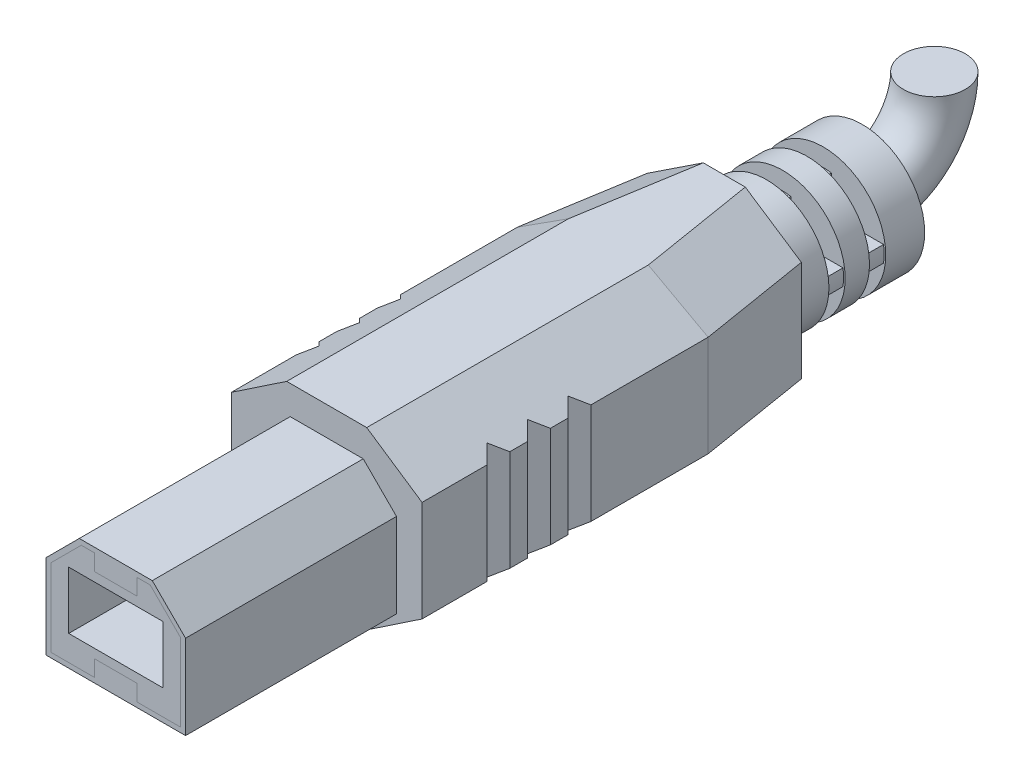
SolidWorks part; units mm, degrees
ref_plane "Front" through (0, 0, 0) normal (0, 0, 1) x (1, 0, 0)
ref_plane "Top" through (0, 0, 0) normal (0, 1, 0) x (1, 0, 0)
ref_plane "Right" through (0, 0, 0) normal (1, 0, 0) x (0, 0, -1)
sketch "Sketch1" plane through (0, 0, 0) normal (0, 0, 1) x (1, 0, 0)
  line L5 (0, 0) -> (-4.3, 0)
  line L6 (-4.3, 0) -> (-4.3, 5.2)
  line L10 (-4.3, 5.2) -> (-2.25, 7.25)
  line L11 (-2.25, 7.25) -> (0, 7.25)
  line L12 (0, 7.25) -> (0, 0)
  line L13 (0, 5.395) -> (-2.9, 5.395)
  line L14 (-2.9, 5.395) -> (-2.9, 1.855)
  line L15 (-2.9, 1.855) -> (0, 1.855)
  line L16 (0, 5.95) -> (-1.3, 5.95)
  line L17 (-1.3, 5.95) -> (-1.3, 6.95)
  line L18 (0, 1.3) -> (-1.3, 1.3)
  line L19 (-1.3, 1.3) -> (-1.3, 0.3)
  line L20 (-2.1257, 6.95) -> (-1.3, 6.95)
  line L21 (-0.3, 6.95) -> (-0.3, 0.3) construction
  line L22 (-1.3, 0.3) -> (-4, 0.3)
  line L23 (-4, 0.3) -> (-4, 5.0757)
  line L24 (-4, 5.0757) -> (-2.1257, 6.95)
  line L25 (-0.3, 0.3) -> (-4, 0.3) construction
  line L26 (-2.1257, 6.95) -> (-0.3, 6.95) construction
  line L27 (-1.3, 6.95) -> (-0.3, 6.95) construction
  line L28 (-1.3, 1.3) -> (-1.3, 1.855)
  line L29 (-0.3, 0.3) -> (-1.3, 0.3) construction
  line L31 (-1.3, 5.395) -> (-1.3, 5.95)
  dimension "D1" = 0.3
  dimension "D2" = 1.3
  dimension "D4" = 3.54
  dimension "D3" = 1.3
  dimension "D5" = 2.9
  dimension "D6" = 7.25
  dimension "D7" = 4.3
  dimension "D8" = 225
  dimension "D9" = 2.25
extrude "Boss-Extrude1" add sketch "Sketch1" against normal blind 13 contours L13 L31 L17 L20 L24 L23 L22 L19 L28 L15 L14 | L28 L18 L12 L15 | L23 L24 L20 L17 L16 L12 L11 L10 L6 L5 L18 L19 L22 | L31 L13 L12 L16
sketch "Sketch2" plane through (0, 0, 0) normal (0, 0, 1) x (1, 0, 0)
  line L0 (0, 5.95) -> (-1.3, 5.95)
  line L1 (-1.3, 5.95) -> (-1.3, 6.95)
  line L2 (-1.3, 6.95) -> (-2.1257, 6.95)
  line L3 (-2.1257, 6.95) -> (-4, 5.0757)
  line L4 (-4, 5.0757) -> (-4, 0.3)
  line L5 (-4, 0.3) -> (-1.3, 0.3)
  line L6 (-1.3, 0.3) -> (-1.3, 1.3)
  line L7 (-1.3, 1.3) -> (0, 1.3)
split line "Split Line4"
mirror "Mirror1" about plane through (0, 0, -13) normal (-1, 0, 0) of bodies 115
sketch "Sketch3" plane through (0, 0, -13) normal (0, 0, -1) x (-1, 0, 0)
  line L0 (-5.875, 7.125) -> (-3.0438, 9.025) construction
  line L1 (-3.0438, 9.025) -> (3.0438, 9.025)
  line L2 (-5.875, 7.125) -> (-5.875, 0.125)
  line L3 (-3.0438, -1.775) -> (3.0438, -1.775)
  line L4 (5.875, 7.125) -> (5.875, 0.125)
  line L5 (3.0438, 9.025) -> (5.875, 7.125) construction
  line L6 (5.875, 0.125) -> (3.0438, -1.775) construction
  line L7 (0, 0) -> (0, -1.775) construction
  line L8 (-3.0438, -1.775) -> (-5.875, 0.125) construction
  line L9 (0, 9.025) -> (0, 7.25)
  line L10 (-5.875, 7.125) -> (-5.875, 9.025)
  line L11 (2.25, 7.25) -> (-2.25, 7.25) construction
  line L12 (-5.875, 9.025) -> (-3.0438, 9.025)
  line L13 (3.0438, 9.025) -> (5.875, 9.025)
  line L14 (5.875, 9.025) -> (5.875, 7.125)
  line L15 (5.875, 0.125) -> (5.875, -1.775)
  line L16 (5.875, -1.775) -> (3.0438, -1.775)
  line L17 (-3.0438, -1.775) -> (-5.875, -1.775)
  line L18 (-5.875, -1.775) -> (-5.875, 0.125)
  line L19 (0, 7.25) -> (0, 3.625)
  line L20 (0, 3.625) -> (5.875, 3.625)
  line M13 (4.3, 0) -> (4.3, 5.2)
  line M14 (4.3, 5.2) -> (2.25, 7.25)
  line M15 (2.25, 7.25) -> (-2.25, 7.25)
  line M17 (-2.9, 5.395) -> (2.9, 5.395)
  line M18 (2.9, 5.395) -> (2.9, 1.855)
  dimension "D1" = 12.36
  dimension "D2" = 12.36
  dimension "D3" = 11.75
  dimension "D4" = 10.8
  dimension "D5" = 7
extrude "Boss-Extrude2" add sketch "Sketch3" along normal blind 24.5 contours L19 L20 M18 M17 | L20 L19 M18 M13 M14 M15 M17 | L20 L4 L14 L13 L1 L9 M13 M15 M14
sketch "Sketch4" plane through (0, 9.025, 0) normal (0, 1, 0) x (1, 0, 0)
  line L0 (0, 37.5) -> (0, 13) construction
  line L4 (-4.75, 37.5) -> (-5.875, 30.63)
  line L5 (-5.875, 37.5) -> (-5.875, 13) construction
  line L8 (-4.75, 37.5) -> (-5.875, 37.5)
  line L9 (-5.875, 37.5) -> (-5.875, 30.63)
  line L14 (-5.875, 23.4071) -> (-5.1679, 22.7)
  line L15 (-5.1679, 22.7) -> (-5.875, 21.9929)
  line L16 (-5.1679, 22.7) -> (-5.875, 22.7) construction
  line L17 (-5.875, 23.4071) -> (-5.875, 21.9929)
  line L18 (-5.1679, 20.2) -> (-5.875, 19.4929)
  line L19 (-5.875, 20.9071) -> (-5.1679, 20.2)
  line L20 (-5.875, 20.9071) -> (-5.875, 19.4929)
  line L21 (-5.1679, 17.7) -> (-5.875, 16.9929)
  line L22 (-5.875, 18.4071) -> (-5.1679, 17.7)
  line L23 (-5.875, 18.4071) -> (-5.875, 16.9929)
  line L34 (0, 37.5) -> (-5.875, 37.5) construction
  dimension "D1" = 17.63
  dimension "D2" = 4.75
  dimension "D3" = 1
  dimension "D4" = 9.7
  dimension "D6" = 2.5
  dimension "D5" = 3
extrude "Cut-Extrude1" cut sketch "Sketch4" against normal through all
chamfer "Chamfer1" distance 3.41 angle 33.86 3 edges at (-5.875, 9.025, -14.9964) (-5.875, 9.025, -27.0186) (-5.3125, 9.025, -34.065)
ref_plane "Plane1" through (0, 0, -13) normal (0, 0, 1) x (1, 0, 0)
split "Split1" trim tools "Plane1" bodies to split 118 resulting bodies 120 121
ref_plane "Plane2" through (0, 3.625, 0) normal (0, -1, 0) x (-1, 0, 0)
mirror "Mirror9" about plane through (0, 0, -37.5) normal (-1, 0, 0) of bodies 121
mirror "Mirror10" about plane through (0, 3.625, -37.5) normal (0, 1, 0) of bodies 122
combine bodies "Combine1" operation type add bodies to combine 123 120
sketch "Sketch7" plane through (0, 3.625, 0) normal (0, 1, 0) x (1, 0, 0)
  line L0 (0, 37.5) -> (0, 40.1)
  line L1 (1.2946, 37.5) -> (-1.2946, 37.5) construction
  line L2 (0, 37.5) -> (3.85, 37.5)
  line L3 (3.85, 37.5) -> (3.85, 40.1)
  line L4 (3.85, 40.1) -> (0, 40.1)
  line L5 (0, 41.1) -> (3.85, 41.1)
  line L6 (3.85, 41.1) -> (3.85, 42.6)
  line L7 (3.85, 42.6) -> (0, 42.6)
  line L8 (0, 43.6) -> (3.85, 43.6)
  line L9 (3.85, 43.6) -> (3.85, 46)
  line L10 (3.85, 46) -> (0, 46)
  line L11 (3.85, 43.6) -> (3.85, 42.6) construction
  line L12 (3.85, 41.1) -> (3.85, 40.1) construction
  line L13 (0, 43.6) -> (0, 46)
  line L14 (0, 41.1) -> (0, 42.6)
  dimension "D1" = 2.6
  dimension "D2" = 1.5
  dimension "D3" = 2.4
  dimension "D4" = 1
  dimension "D5" = 3.85
revolve "Revolve1" add sketch "Sketch7" angle 360 about L13
sketch "Sketch5" plane through (0, 0, -37.5) normal (0, 0, -1) x (-1, 0, 0)
  line L0 (0, 3.625) -> (0, 6.375) construction
  line L1 (-4.75, 6.737) -> (4.75, 6.737) construction
  line L2 (-4.75, 6.737) -> (-4.75, 0.513) construction
  line L3 (-4.75, 0.513) -> (4.75, 0.513) construction
  line L4 (4.75, 6.737) -> (4.75, 0.513) construction
  line L5 (-4.75, 6.737) -> (4.75, 0.513) construction
  line L6 (-4.75, 0.513) -> (4.75, 6.737) construction
  line L7 (-0.5, 6.3292) -> (-0.5, 4.125)
  line L8 (-0.5, 4.125) -> (-3.7165, 4.125)
  line L9 (0, 3.625) -> (-3.75, 3.625) construction
  line L10 (-0.5, 4.125) -> (0, 4.125) construction
  line L12 (-0.5, 3.625) -> (-0.5, 4.125) construction
  line L13 (0.5, 4.125) -> (3.7165, 4.125)
  line L14 (0.5, 6.3292) -> (0.5, 4.125)
  line L15 (0.5, 3.125) -> (3.7165, 3.125)
  line L16 (0.5, 0.9208) -> (0.5, 3.125)
  line L17 (-0.5, 0.9208) -> (-0.5, 3.125)
  line L18 (-0.5, 3.125) -> (-3.7165, 3.125)
  arc A0 (0.5, 6.3292) -> (-0.5, 6.3292) centre (0, 3.625) ccw
  arc A1 (-3.7165, 4.125) -> (-3.7165, 3.125) centre (0, 3.625) ccw
  arc A2 (3.7165, 4.125) -> (3.7165, 3.125) centre (0, 3.625) cw
  arc A3 (0.5, 0.9208) -> (-0.5, 0.9208) centre (0, 3.625) cw
  point P0 (0, 3.625)
  dimension "D2" = 3.75
  dimension "D3" = 2.75
  dimension "D1" = 0.5
extrude "Boss-Extrude3" add sketch "Sketch5" along normal blind 6.25
sketch "Sketch8" plane through (0, 0, -46) normal (0, 0, -1) x (-1, 0, 0)
  line L0 (0, 1.72) -> (0, 8.07) construction
  line L1 (-4.5023, 8.07) -> (4.5023, 8.07) construction
  circle A0 centre (0, 3.625) radius 1.905
  point P9 (0, 8.07)
  dimension "D2" = 3.81
  dimension "D1" = 6.35
revolve "Revolve2" add sketch "Sketch8" angle 90 about L1
